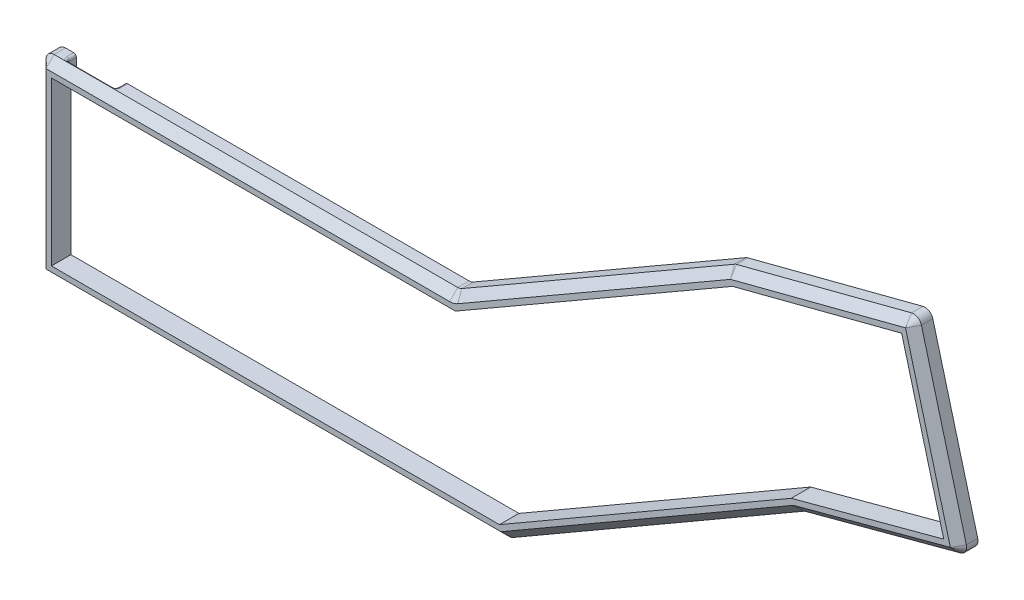
SolidWorks part; units mm, degrees
ref_plane "Plan de face" through (0, 0, 0) normal (0, 0, 1) x (1, 0, 0)
ref_plane "Plan de dessus" through (0, 0, 0) normal (0, 1, 0) x (1, 0, 0)
ref_plane "Plan de droite" through (0, 0, 0) normal (1, 0, 0) x (0, 0, -1)
sketch "Esquisse1" plane through (0, 0, 0) normal (0, 0, 1) x (1, 0, 0)
  line L0 (152.8114, 25.9717) -> (138.2826, 80.2215) construction
  line L1 (98.1506, 11.3316) -> (152.8114, 25.9717) construction
  line L2 (-9.3986, -50.8585) -> (98.1506, 11.3316) construction
  line L3 (-172.3739, -50.8585) -> (-9.3986, -50.8585) construction
  line L4 (-24.5886, 5.3017) -> (-172.3739, 5.2915) construction
  line L5 (138.2826, 80.2215) -> (78.0109, 64.5416) construction
  line L6 (-151.6088, 5.3124) -> (-151.6088, 5.2929)
  line L7 (-24.5886, 5.3017) -> (78.0109, 64.5416) construction
  line L8 (-172.3739, 5.2915) -> (-172.3739, -50.6876) construction
  line L9 (-172.3739, -50.6876) -> (-172.3739, -50.8585) construction
  line L10 (-25.1245, 7.3016) -> (-174.3739, 7.2914)
  line L11 (-174.3739, 7.2914) -> (-174.3739, -50.6876)
  line L12 (-174.3739, -50.6876) -> (-174.3739, -52.8585)
  line L13 (-174.3739, -52.8585) -> (-8.862, -52.8585)
  line L14 (-8.862, -52.8585) -> (98.9231, 9.4681)
  line L15 (98.9231, 9.4681) -> (155.2607, 24.5572)
  line L16 (155.2607, 24.5572) -> (139.7008, 82.657)
  line L17 (139.7008, 82.657) -> (77.2454, 66.409)
  line L18 (-25.1245, 7.3016) -> (77.2454, 66.409)
  line L19 (-26.4645, 12.3015) -> (-179.3739, 12.291)
  line L20 (-179.3739, 12.291) -> (-179.3739, -50.6876)
  line L21 (-179.3739, -50.6876) -> (-179.3739, -57.8585)
  line L22 (-179.3739, -57.8585) -> (-7.5204, -57.8585)
  line L23 (-7.5204, -57.8585) -> (100.8545, 4.8091)
  line L24 (100.8545, 4.8091) -> (161.3839, 21.021)
  line L25 (161.3839, 21.021) -> (143.2464, 88.7459)
  line L26 (143.2464, 88.7459) -> (75.3314, 71.0775)
  line L27 (-26.4645, 12.3015) -> (75.3314, 71.0775)
  circle A0 centre (80.6856, 58.4893) radius 1
  circle A1 centre (92.8776, 28.0855) radius 1
  circle A2 centre (-29.7028, -2.6485) radius 1
  circle A3 centre (-10.6528, -46.4381) radius 1
  circle A4 centre (-114.2594, -13.4181) radius 1
  circle A5 centre (-114.0308, -32.4935) radius 1
  dimension "D1" = 2
  dimension "D2" = 5
extrude "Boss.-Extru.1" add sketch "Esquisse1" along normal blind 7.2 contours L27 L19 L20 L21 L22 L23 L24 L25 L26 L10 L18 L17 L16 L15 L14 L13 L12 L11 region at (26.2883, 38.477, 0)
fillet "Congé1" radius 3 8 edges at (-179.3739, -57.8585, 3.6) (-7.5204, -57.8585, 3.6) (100.8545, 4.8091, 3.6) (161.3839, 21.021, 3.6) (143.2464, 88.7459, 3.6) (75.3314, 71.0775, 3.6) (-26.4645, 12.3015, 3.6) (-179.3739, 12.291, 3.6)
sketch "Esquisse2" plane through (0, 0, 0) normal (0, 0, 1) x (1, 0, 0)
  circle A0 centre (158.2016, 22.9581) radius 1
  circle A1 centre (141.3885, 85.5343) radius 1
  circle A2 centre (76.5002, 68.7766) radius 1
  circle A3 centre (99.8904, 7.0714) radius 1
  circle A4 centre (-8.1724, -55.2759) radius 1
  circle A5 centre (-25.6914, 9.9201) radius 1
  circle A6 centre (-176.5621, 9.9201) radius 1
  circle A7 centre (-177.0296, -55.2759) radius 1
extrude "Enlèv. mat.-Extru.1" cut sketch "Esquisse2" along normal blind 5.2
chamfer "Chanfrein1" distance 3 angle 45 16 edges at (-178.4953, 11.4125, 7.2) (-101.8212, 12.2964, 7.2) (-26.4919, 12.4038, 7.2) (24.6056, 41.7889, 7.2) (75.3418, 71.0522, 7.2) (108.0441, 79.5878, 7.2) (142.6286, 87.6851, 7.2) (152.3124, 54.8937, 7.2) (160.3079, 21.6424, 7.2) (129.8616, 12.5782, 7.2) (100.8645, 4.785, 7.2) (46.844, -26.4224, 7.2) (-7.5479, -57.756, 7.2) (-92.3496, -57.8585, 7.2) (-178.4952, -56.9798, 7.2) (-179.3739, -22.7836, 7.2)
sketch "Esquisse3" plane through (-0.0008, 12.3034, 0) normal (-0.0001, 1, 0) x (1, 0.0001, 0)
  line L0 (-176.3732, 0) -> (-176.3732, -4.2) construction
  line L1 (-172.3732, 0) -> (-154.3732, 0)
  line L2 (-172.3732, 0) -> (-172.3732, -2.5)
  line L3 (-171.3732, -3.5) -> (-155.3732, -3.5)
  line L4 (-154.3732, 0) -> (-154.3732, -2.5)
  line L5 (-27.2675, 0) -> (-176.3732, 0) construction
  arc A0 (-155.3732, -3.5) -> (-154.3732, -2.5) centre (-155.3732, -2.5) ccw
  arc A1 (-172.3732, -2.5) -> (-171.3732, -3.5) centre (-171.3732, -2.5) ccw
  point P10 (-154.3732, -3.5)
  dimension "D5" = 1
  dimension "D1" = 4
  dimension "D2" = 18
  dimension "D3" = 0
  dimension "D4" = 3.5
extrude "Enlèv. mat.-Extru.2" cut sketch "Esquisse3" against normal blind 10
fillet "Congé2" radius 1 4 edges at (-172.3741, 12.2915, 1.25) (-172.0812, 12.2915, 3.2071) (-154.3741, 12.2928, 1.25) (-154.667, 12.2927, 3.2071)
sketch "Esquisse4" plane through (0, 0, 0) normal (0, 0, 1) x (1, 0, 0)
  line L0 (155.2607, 24.5572) -> (154.4846, 27.4551)
  line L1 (155.2607, 24.5572) -> (139.7008, 82.657) construction
  line L2 (155.2607, 24.5572) -> (152.3628, 23.7811)
  line L3 (98.9231, 9.4681) -> (155.2607, 24.5572) construction
  line L4 (154.4846, 27.4551) -> (152.3628, 23.7811)
  dimension "D1" = 3
  dimension "D2" = 3
extrude "Boss.-Extru.2" add sketch "Esquisse4" along normal blind 0.6
